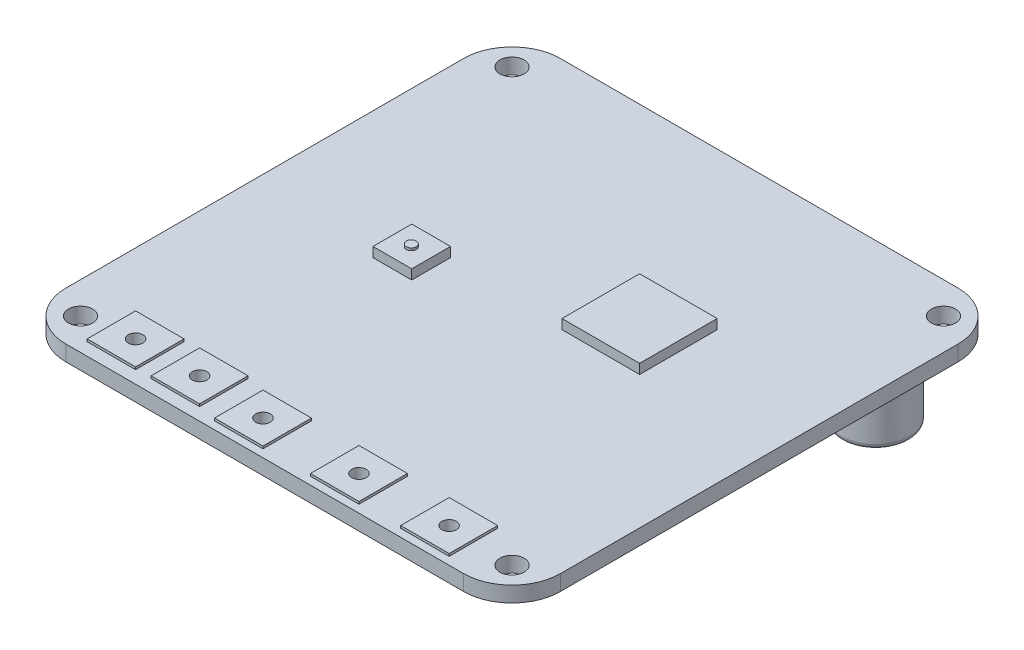
SolidWorks part; units mm, degrees
material "ABS"
ref_plane "Alzado" through (0, 0, 0) normal (0, 0, 1) x (1, 0, 0)
ref_plane "Planta" through (0, 0, 0) normal (0, 1, 0) x (1, 0, 0)
ref_plane "Vista lateral" through (0, 0, 0) normal (1, 0, 0) x (0, 0, -1)
sketch "Croquis1" plane through (0, 0, 0) normal (0, 1, 0) x (1, 0, 0)
  line L1 (-25.5, 25.5) -> (25.5, 25.5)
  line L2 (-25.5, 25.5) -> (-25.5, -25.5)
  line L3 (-25.5, -25.5) -> (25.5, -25.5)
  line L4 (25.5, 25.5) -> (25.5, -25.5)
  line L5 (-25.5, 25.5) -> (25.5, -25.5) construction
  line L6 (-25.5, -25.5) -> (25.5, 25.5) construction
  point P0 (0, 0)
  dimension "D1" = 51
  dimension "D2" = 51
extrude "Saliente-Extruir1" add sketch "Croquis1" against normal blind 1.6
fillet "Redondeo1" radius 5 4 edges at (25.5, -0.8, -25.5) (-25.5, -0.8, -25.5) (-25.5, -0.8, 25.5) (25.5, -0.8, 25.5)
sketch "Croquis2" plane through (0, 0, 0) normal (0, 1, 0) x (1, 0, 0)
  line L0 (-25.5, 20.5) -> (-25.5, -20.5) construction
  line L1 (-12.3871, 2.0474) -> (-8.3871, 2.0474)
  line L2 (-12.3871, 2.0474) -> (-12.3871, -1.9526)
  line L3 (-12.3871, -1.9526) -> (-8.3871, -1.9526)
  line L4 (-8.3871, 2.0474) -> (-8.3871, -1.9526)
  line L5 (-12.3871, 2.0474) -> (-8.3871, -1.9526) construction
  line L6 (-12.3871, -1.9526) -> (-8.3871, 2.0474) construction
  line L7 (3.8, 9.359) -> (11.8, 9.359)
  line L8 (3.8, 9.359) -> (3.8, 1.359)
  line L9 (3.8, 1.359) -> (11.8, 1.359)
  line L10 (11.8, 9.359) -> (11.8, 1.359)
  line L11 (3.8, 9.359) -> (11.8, 1.359) construction
  line L12 (3.8, 1.359) -> (11.8, 9.359) construction
  line L13 (25.5, -20.5) -> (25.5, 20.5) construction
  point P0 (-10.3871, 0.0474)
  point P5 (7.8, 5.359)
  point P12 (-25.5, 0)
  dimension "D1" = 15.113
  dimension "D2" = 4
  dimension "D3" = 8
  dimension "D4" = 17.7
extrude "Saliente-Extruir2" add sketch "Croquis2" along normal blind 1
sketch "Croquis3" plane through (0, 0, 0) normal (0, 1, 0) x (1, 0, 0)
  line L1 (22.25, 22.25) -> (-22.25, 22.25) construction
  line L2 (22.25, 22.25) -> (22.25, -22.25) construction
  line L3 (22.25, -22.25) -> (-22.25, -22.25) construction
  line L4 (-22.25, 22.25) -> (-22.25, -22.25) construction
  line L5 (22.25, 22.25) -> (-22.25, -22.25) construction
  line L6 (22.25, -22.25) -> (-22.25, 22.25) construction
  circle A0 centre (-22.25, 22.25) radius 1.25
  circle A1 centre (-22.25, -22.25) radius 1.25
  circle A2 centre (22.25, -22.25) radius 1.25
  circle A3 centre (22.25, 22.25) radius 1.25
  point P0 (0, 0)
  dimension "D2" = 2.5
  dimension "D1" = 44.5
extrude "Cortar-Extruir1" cut sketch "Croquis3" against normal through all
sketch "Croquis4" plane through (0, 0, 0) normal (0, 1, 0) x (1, 0, 0)
  line L0 (-20.5, -25.5) -> (20.5, -25.5) construction
  line L1 (-5.98, -19.7) -> (-0.98, -19.7)
  line L2 (-5.98, -19.7) -> (-5.98, -24.7)
  line L3 (-5.98, -24.7) -> (-0.98, -24.7)
  line L4 (-0.98, -19.7) -> (-0.98, -24.7)
  line L5 (-5.98, -19.7) -> (-0.98, -24.7) construction
  line L6 (-5.98, -24.7) -> (-0.98, -19.7) construction
  line L7 (3.92, -19.7) -> (8.92, -19.7)
  line L8 (3.92, -19.7) -> (3.92, -24.7)
  line L9 (3.92, -24.7) -> (8.92, -24.7)
  line L10 (8.92, -19.7) -> (8.92, -24.7)
  line L11 (3.92, -19.7) -> (8.92, -24.7) construction
  line L12 (3.92, -24.7) -> (8.92, -19.7) construction
  line L13 (13.22, -19.7) -> (18.22, -19.7)
  line L14 (13.22, -19.7) -> (13.22, -24.7)
  line L15 (13.22, -24.7) -> (18.22, -24.7)
  line L16 (18.22, -19.7) -> (18.22, -24.7)
  line L17 (13.22, -19.7) -> (18.22, -24.7) construction
  line L18 (13.22, -24.7) -> (18.22, -19.7) construction
  line L19 (25.5, -20.5) -> (25.5, 20.5) construction
  line L20 (-25.5, 20.5) -> (-25.5, -20.5) construction
  line L21 (-13.02, -19.2) -> (-8.02, -19.2)
  line L22 (-13.02, -19.2) -> (-13.02, -24.2)
  line L23 (-13.02, -24.2) -> (-8.02, -24.2)
  line L24 (-8.02, -19.2) -> (-8.02, -24.2)
  line L25 (-13.02, -19.2) -> (-8.02, -24.2) construction
  line L26 (-13.02, -24.2) -> (-8.02, -19.2) construction
  line L27 (-19.62, -19.2) -> (-14.62, -19.2)
  line L28 (-19.62, -19.2) -> (-19.62, -24.2)
  line L29 (-19.62, -24.2) -> (-14.62, -24.2)
  line L30 (-14.62, -19.2) -> (-14.62, -24.2)
  line L31 (-19.62, -19.2) -> (-14.62, -24.2) construction
  line L32 (-19.62, -24.2) -> (-14.62, -19.2) construction
  point P0 (-3.48, -22.2)
  point P5 (6.42, -22.2)
  point P10 (15.72, -22.2)
  point P17 (0, -25.5)
  point P18 (-17.12, -21.7)
  point P21 (-10.52, -21.7)
  dimension "D1" = 3.3
  dimension "D2" = 5
  dimension "D3" = 9.9
  dimension "D4" = 9.3
  dimension "D5" = 9.78
  dimension "D6" = 5
  dimension "D7" = 3.8
  dimension "D8" = 6.6
  dimension "D9" = 8.38
extrude "Saliente-Extruir3" add sketch "Croquis4" along normal blind 0.25
sketch "Croquis5" plane through (0, 0.25, 0) normal (0, 1, 0) x (1, 0, 0)
  line L0 (-0.98, -19.7) -> (-5.98, -19.7) construction
  line L1 (-5.98, -19.7) -> (-5.98, -24.7) construction
  line L2 (8.92, -19.7) -> (3.92, -19.7) construction
  line L3 (18.22, -19.7) -> (13.22, -19.7) construction
  line L4 (-8.02, -19.2) -> (-13.02, -19.2) construction
  line L5 (-8.02, -24.2) -> (-8.02, -19.2) construction
  line L6 (-14.62, -19.2) -> (-19.62, -19.2) construction
  circle A0 centre (-3.48, -22.2) radius 0.75
  circle A1 centre (6.42, -22.2) radius 0.75
  circle A2 centre (15.72, -22.2) radius 0.75
  circle A3 centre (-10.52, -21.7) radius 0.75
  circle A4 centre (-17.12, -21.7) radius 0.75
  point P9 (-3.48, -19.7)
  point P12 (-5.98, -22.2)
  point P16 (6.42, -19.7)
  point P19 (15.72, -19.7)
  point P24 (-10.52, -19.2)
  point P27 (-8.02, -21.7)
  point P30 (-17.12, -19.2)
  dimension "D1" = 1.5
extrude "Cortar-Extruir2" cut sketch "Croquis5" against normal through all
sketch "Croquis6" plane through (0, -1.6, 0) normal (0, 1, 0) x (1, 0, 0)
  line L0 (20.5, 25.5) -> (-20.5, 25.5) construction
  line L1 (-25.5, 20.5) -> (-25.5, -20.5) construction
  line L2 (25.5, -20.5) -> (25.5, 20.5) construction
  circle A0 centre (-15.2, 22.84) radius 3.5
  circle A1 centre (14.65, 22.84) radius 3.5
  dimension "D1" = 7
  dimension "D2" = 2.66
  dimension "D3" = 10.3
  dimension "D4" = 10.85
extrude "Saliente-Extruir4" add sketch "Croquis6" against normal blind 12
fillet "Redondeo2" radius 0.5 2 edges at (14.65, -13.6, -19.34) (-15.2, -13.6, -19.34)
sketch "Croquis7" plane through (0, -1.6, 0) normal (0, -1, 0) x (1, 0, 0)
  line L0 (-20.5, 25.5) -> (20.5, 25.5) construction
  line L1 (-22.5, -16.02) -> (15.6, -16.02)
  line L2 (-22.5, -16.02) -> (-22.5, -18.56)
  line L3 (-22.5, -18.56) -> (15.6, -18.56)
  line L4 (15.6, -16.02) -> (15.6, -18.56)
  line L5 (-22.5, -16.02) -> (15.6, -18.56) construction
  line L6 (-22.5, -18.56) -> (15.6, -16.02) construction
  line L7 (-22.5, 9.33) -> (15.6, 9.33)
  line L8 (-22.5, 9.33) -> (-22.5, 6.79)
  line L9 (-22.5, 6.79) -> (15.6, 6.79)
  line L10 (15.6, 9.33) -> (15.6, 6.79)
  line L11 (-22.5, 9.33) -> (15.6, 6.79) construction
  line L12 (-22.5, 6.79) -> (15.6, 9.33) construction
  line L13 (-25.5, -20.5) -> (-25.5, 20.5) construction
  point P0 (-3.45, -17.29)
  point P5 (-3.45, 8.06)
  dimension "D1" = 17.44
  dimension "D2" = 25.35
  dimension "D3" = 38.1
  dimension "D4" = 2.54
  dimension "D5" = 2.54
  dimension "D6" = 3
extrude "Saliente-Extruir5" add sketch "Croquis7" along normal blind 8
sketch "Croquis8" plane through (0, 1, 0) normal (0, 1, 0) x (1, 0, 0)
  line L0 (-8.3871, 2.0474) -> (-12.3871, 2.0474) construction
  circle A0 centre (-10.3871, 0) radius 0.5121
  point P5 (-10.3871, 2.0474)
extrude "Saliente-Extruir6" add sketch "Croquis8" along normal blind 0.25
